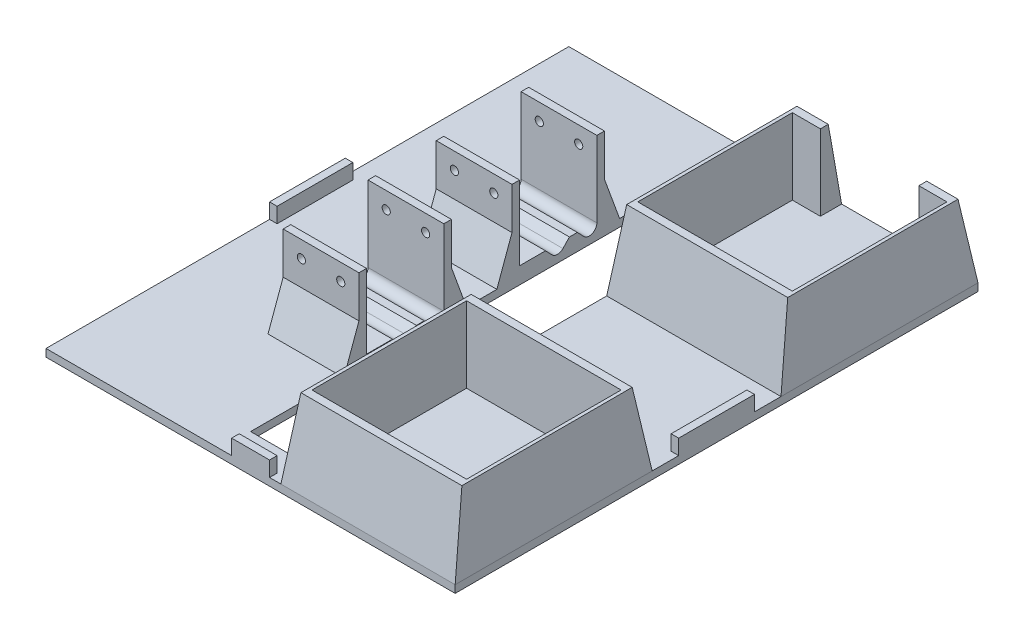
SolidWorks part; units mm, degrees
ref_plane "Front Plane" through (0, 0, 0) normal (0, 0, 1) x (1, 0, 0)
ref_plane "Top Plane" through (0, 0, 0) normal (0, 1, 0) x (1, 0, 0)
ref_plane "Right Plane" through (0, 0, 0) normal (1, 0, 0) x (0, 0, -1)
sketch "Sketch1" plane through (0, 0, 0) normal (0, 1, 0) x (1, 0, 0)
  line L1 (0, 0) -> (115, 0)
  line L2 (0, 0) -> (0, 345)
  line L3 (0, 345) -> (115, 345)
  line L5 (155, 345) -> (270, 345)
  line L7 (155, 0) -> (270, 0)
  line L8 (270, 345) -> (270, 0)
  line L9 (115, 345) -> (155, 345)
  line L11 (115, 325) -> (155, 325)
  line L13 (115, 20) -> (155, 20)
  line L17 (155, 325) -> (155, 20)
  line L18 (115, 20) -> (115, 325)
  line L20 (115, 345) -> (115, 325) construction
  line L21 (115, 20) -> (115, 0) construction
  line L22 (115, 0) -> (155, 0)
  dimension "D1" = 345
  dimension "D2" = 270
  dimension "D3" = 40
  dimension "D4" = 20
  dimension "D5" = 20
extrude "Boss-Extrude1" add sketch "Sketch1" along normal blind 5
sketch "Sketch2" plane through (0, 5, 0) normal (0, 1, 0) x (1, 0, 0)
  line L1 (65, 253.5) -> (115, 253.5)
  line L2 (65, 253.5) -> (65, 248.5)
  line L3 (65, 248.5) -> (115, 248.5)
  line L4 (115, 253.5) -> (115, 248.5)
  line L5 (65, 197.5) -> (115, 197.5)
  line L6 (65, 197.5) -> (65, 192.5)
  line L7 (65, 192.5) -> (115, 192.5)
  line L8 (115, 197.5) -> (115, 192.5)
  line L9 (115, 325) -> (115, 20) construction
  line L10 (0, 172.5) -> (270, 172.5) construction
  line L12 (65, 152.5) -> (115, 152.5)
  line L13 (115, 147.5) -> (115, 152.5)
  line L14 (65, 147.5) -> (115, 147.5)
  line L15 (65, 147.5) -> (65, 152.5)
  line L16 (65, 96.5) -> (115, 96.5)
  line L17 (115, 91.5) -> (115, 96.5)
  line L18 (65, 91.5) -> (115, 91.5)
  line L19 (65, 91.5) -> (65, 96.5)
  line L21 (270, 0) -> (270, 345) construction
  line L22 (0, 345) -> (0, 0) construction
  dimension "D1" = 5
  dimension "D2" = 51
  dimension "D3" = 50
  dimension "D4" = 40
extrude "Boss-Extrude2" add sketch "Sketch2" along normal blind 55
chamfer "Chamfer1" distance 10 angle 70 4 edges at (90, 5, -91.5) (90, 5, -152.5) (90, 5, -192.5) (90, 5, -253.5) first distance on face at (135, 5, -172.5)
sketch "Sketch4" plane through (115, 0, 0) normal (1, 0, 0) x (0, 0, -1)
  line L0 (147.5, 60) -> (147.5, 5) construction
  line L1 (96.5, 5) -> (147.5, 5)
  line L2 (96.5, 5) -> (96.5, 11)
  line L3 (96.5, 11) -> (147.5, 11)
  line L4 (147.5, 5) -> (147.5, 11)
  line L5 (142.5, 5) -> (142.5, 11) construction
  line L6 (134.601, 11) -> (138.4184, 7.112)
  line L7 (134.601, 11) -> (137.601, 11)
  line L8 (147.5, 10) -> (96.5, 10) construction
  line L9 (125.1038, 6.534) -> (129.399, 11)
  line L10 (129.399, 11) -> (126.399, 11)
  line L11 (117.8962, 6.534) -> (113.601, 11)
  line L12 (113.601, 11) -> (116.601, 11)
  line L13 (172.5, 5) -> (172.5, 54.1934) construction
  line L14 (182.5, 5) -> (162.5, 5) construction
  line L19 (197.5, 5) -> (248.5, 5)
  line L20 (197.5, 5) -> (197.5, 11)
  line L21 (197.5, 11) -> (248.5, 11)
  line L22 (248.5, 5) -> (248.5, 11)
  line L23 (243.5, 5) -> (243.5, 11) construction
  line L24 (235.601, 11) -> (239.8962, 6.534)
  line L25 (235.601, 11) -> (238.601, 11)
  line L26 (248.5, 10) -> (197.5, 10) construction
  line L27 (226.1038, 6.534) -> (230.399, 11)
  line L28 (230.399, 11) -> (227.399, 11)
  line L29 (218.8962, 6.534) -> (214.601, 11)
  line L30 (214.601, 11) -> (217.601, 11)
  line L31 (248.5, 60) -> (248.5, 5) construction
  line L32 (197.5, 60) -> (197.5, 5) construction
  circle A0 centre (142.5, 10) radius 5
  circle A1 centre (121.5, 10) radius 5
  circle A4 centre (243.5, 10) radius 5
  circle A5 centre (222.5, 10) radius 5
  line M10 (248.5, 5) -> (197.5, 5)
  line M11 (197.5, 5) -> (197.5, 60)
  line M20 (147.5, 5) -> (96.5, 5)
  line M21 (96.5, 5) -> (96.5, 60)
  dimension "D2" = 10
  dimension "D5" = 10
  dimension "D10" = 10
  dimension "D16" = 10
  dimension "D1" = 6
  dimension "D3" = 6
  dimension "D4" = 3
  dimension "D6" = 26
  dimension "D7" = 3
  dimension "D8" = 3
  dimension "D9" = 6
  dimension "D11" = 6
  dimension "D12" = 3
  dimension "D13" = 3
  dimension "D14" = 3
  dimension "D15" = 26
extrude "Boss-Extrude3" add sketch "Sketch4" against normal blind 50 contours A1 L11 L3 M21 M20 | A1 L1 A0 L6 L3 L9 | A0 L4 M20 | A5 L29 L21 M11 M10 | A5 L19 A4 L24 L21 L27 | A4 L22 M10 region at (115, 7.8434, -106.625) region at (115, 7.4388, -132.0131) region at (115, 6.1168, -146.3832) region at (115, 7.8434, -207.625) region at (115, 7.4367, -233) region at (115, 6.1168, -247.3832)
sketch "Sketch3" plane through (0, 0, -248.5) normal (0, 0, 1) x (1, 0, 0)
  line L0 (90, 5) -> (90, 60) construction
  line L1 (65, 5) -> (115, 5) construction
  line L2 (65, 60) -> (115, 60) construction
  line L3 (65, 5) -> (115, 5) construction
  circle A0 centre (77, 49) radius 2.7
  circle A1 centre (103, 49) radius 2.7
  dimension "D3" = 5.4
  dimension "D1" = 13
  dimension "D2" = 44
extrude "Cut-Extrude1" cut sketch "Sketch3" against normal through all both and the other way through all
sketch "Sketch5" plane through (0, 5, 0) normal (0, 1, 0) x (1, 0, 0)
  line L0 (155, 20) -> (155, 325) construction
  line L1 (270, 0) -> (155, 0)
  line L2 (270, 0) -> (270, 130)
  line L3 (270, 130) -> (155, 130)
  line L4 (155, 0) -> (155, 130)
  line L5 (270, 172.5) -> (155, 172.5) construction
  line L6 (161.5, 116) -> (263.5, 116)
  line L7 (161.5, 116) -> (161.5, 14)
  line L8 (161.5, 14) -> (263.5, 14)
  line L9 (263.5, 116) -> (263.5, 14)
  line L10 (270, 0) -> (270, 345) construction
  line L11 (263.5, 229) -> (263.5, 331)
  line L12 (161.5, 331) -> (263.5, 331)
  line L13 (161.5, 229) -> (161.5, 331)
  line L14 (161.5, 229) -> (263.5, 229)
  line L15 (155, 345) -> (155, 215)
  line L16 (270, 215) -> (155, 215)
  line L17 (270, 345) -> (270, 215)
  line L18 (270, 345) -> (155, 345)
  dimension "D1" = 115
  dimension "D2" = 130
  dimension "D3" = 14
  dimension "D4" = 14
  dimension "D5" = 6.5
  dimension "D6" = 6.5
extrude "Boss-Extrude4" add sketch "Sketch5" along normal blind 50
sketch "Sketch6" plane through (0, 0, -345) normal (0, 0, -1) x (-1, 0, 0)
  line L0 (-270, 55) -> (-155, 55) construction
  line L1 (-180, 5) -> (-245, 5)
  line L2 (-180, 5) -> (-180, 55)
  line L3 (-180, 55) -> (-245, 55)
  line L4 (-245, 5) -> (-245, 55)
  line L5 (-155, 55) -> (-155, 5) construction
  line L6 (-270, 55) -> (-270, 0) construction
  dimension "D1" = 25
  dimension "D2" = 25
extrude "Cut-Extrude2" cut sketch "Sketch6" against normal blind 50 and the other way through all
chamfer "Chamfer2" distance 50 angle 10 5 edges at (212.5, 55, -215) (167.5, 55, -345) (257.5, 55, -345) (212.5, 55, 0) (212.5, 55, -130) first distance on face at (212.5, 30, -215) first distance on face at (170, 24, -345) first distance on face at (141.6667, 20, 0) first distance on face at (212.5, 30, -130)
chamfer "Chamfer3" distance 50 angle 5 4 edges at (270, 55, -280) (155, 55, -280) (155, 55, -65) (270, 55, -65) first distance on face at (270, 24, -172.5) first distance on face at (155, 20.8333, -172.5)
sketch "Sketch7" plane through (0, 5, 0) normal (0, 1, 0) x (1, 0, 0)
  line L0 (270, 130) -> (270, 215) construction
  line L1 (270, 197.5) -> (265, 197.5)
  line L2 (270, 197.5) -> (270, 147.5)
  line L3 (270, 147.5) -> (265, 147.5)
  line L4 (265, 197.5) -> (265, 147.5)
  line L5 (155, 345) -> (0, 345) construction
  line L6 (147.5, 345) -> (122.5, 345)
  line L7 (147.5, 345) -> (147.5, 340)
  line L8 (147.5, 340) -> (122.5, 340)
  line L9 (122.5, 345) -> (122.5, 340)
  line L10 (155, 325) -> (115, 325) construction
  line L11 (155, 172.5) -> (115, 172.5) construction
  line L12 (155, 130) -> (155, 215) construction
  line L13 (115, 182.5) -> (115, 162.5) construction
  line L14 (5, 197.5) -> (5, 147.5)
  line L15 (135, 208.8602) -> (135, 147.5) construction
  line L16 (0, 147.5) -> (5, 147.5)
  line L17 (0, 197.5) -> (0, 147.5)
  line L18 (0, 197.5) -> (5, 197.5)
  line L19 (122.5, 0) -> (122.5, 5)
  line L20 (147.5, 5) -> (122.5, 5)
  line L21 (147.5, 0) -> (147.5, 5)
  line L22 (147.5, 0) -> (122.5, 0)
  point P6 (270, 172.5)
  point P13 (135, 345)
  point P16 (135, 325)
  dimension "D1" = 5
  dimension "D2" = 50
  dimension "D3" = 5
  dimension "D4" = 25
  dimension "D5" = 0
extrude "Boss-Extrude5" add sketch "Sketch7" along normal blind 10
